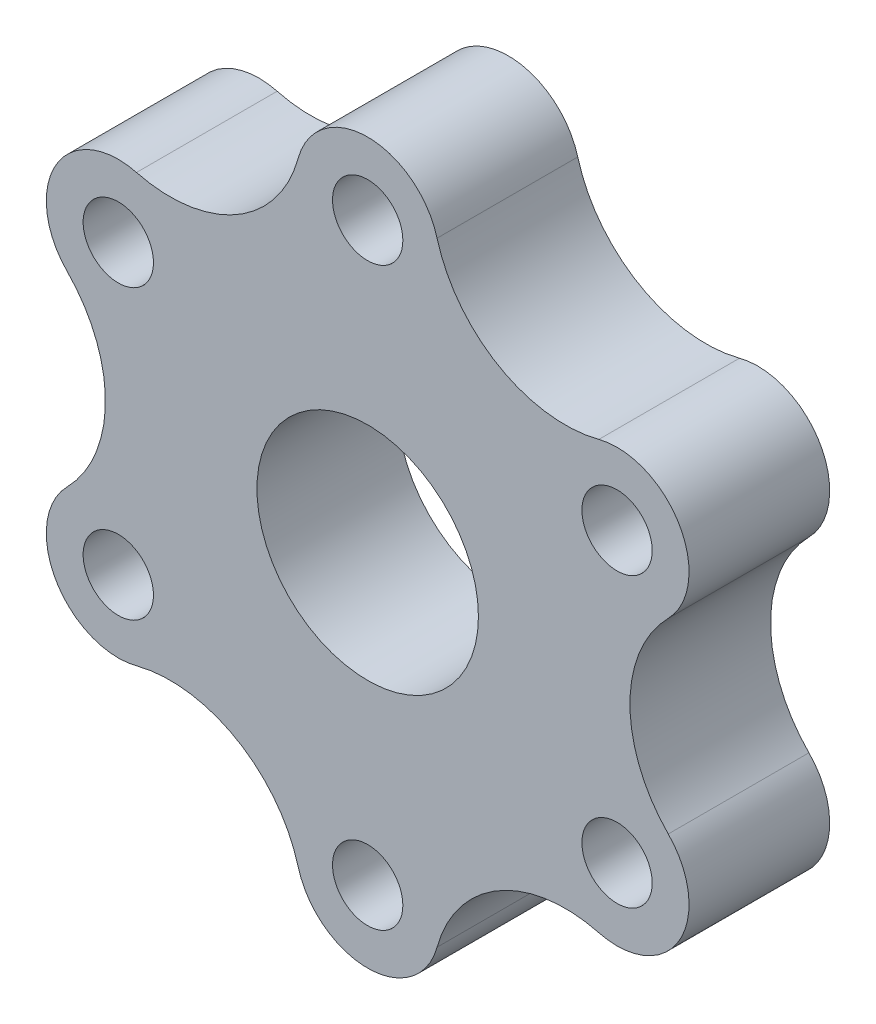
SolidWorks part; units mm, degrees
material "6061-T6 (SS)"
ref_plane "Front Plane" through (0, 0, 0) normal (0, 0, 1) x (1, 0, 0)
ref_plane "Top Plane" through (0, 0, 0) normal (0, 1, 0) x (1, 0, 0)
ref_plane "Right Plane" through (0, 0, 0) normal (1, 0, 0) x (0, 0, -1)
sketch "Sketch1" plane through (0, 0, 0) normal (0, 0, 1) x (1, 0, 0)
  circle A0 centre (0, 0) radius 45 construction
  circle A1 centre (0, 0) radius 37.5 construction
  circle A2 centre (0, 0) radius 10
  arc A3 (6.268, 27.7213) -> (-6.268, 27.7213) centre (0, 26) ccw
  arc A4 (27.1413, 8.4324) -> (20.8734, 19.2888) centre (22.5167, 13) ccw
  arc A5 (20.8734, -19.2888) -> (27.1413, -8.4324) centre (22.5167, -13) ccw
  arc A6 (-6.268, -27.7213) -> (6.268, -27.7213) centre (0, -26) ccw
  arc A7 (-27.1413, -8.4324) -> (-20.8734, -19.2888) centre (-22.5167, -13) ccw
  arc A8 (-20.8734, 19.2888) -> (-27.1413, 8.4324) centre (-22.5167, 13) ccw
  arc A9 (-20.8734, 19.2888) -> (-6.268, 27.7213) centre (-17.8396, 30.899) ccw
  arc A10 (6.268, 27.7213) -> (20.8734, 19.2888) centre (17.8396, 30.899) ccw
  arc A11 (27.1413, 8.4324) -> (27.1413, -8.4324) centre (35.6791, 0) ccw
  arc A12 (20.8734, -19.2888) -> (6.268, -27.7213) centre (17.8396, -30.899) ccw
  arc A13 (-6.268, -27.7213) -> (-20.8734, -19.2888) centre (-17.8396, -30.899) ccw
  arc A14 (-27.1413, -8.4324) -> (-27.1413, 8.4324) centre (-35.6791, 0) ccw
  arc A15 (-27.1413, 8.4324) -> (-20.8734, 19.2888) centre (-22.5167, 13) ccw construction
  arc A16 (-6.268, 27.7213) -> (6.268, 27.7213) centre (0, 26) ccw construction
  arc A17 (20.8734, 19.2888) -> (27.1413, 8.4324) centre (22.5167, 13) ccw construction
  arc A18 (27.1413, -8.4324) -> (20.8734, -19.2888) centre (22.5167, -13) ccw construction
  arc A19 (6.268, -27.7213) -> (-6.268, -27.7213) centre (0, -26) ccw construction
  arc A20 (-20.8734, -19.2888) -> (-27.1413, -8.4324) centre (-22.5167, -13) ccw construction
  circle A21 centre (0, 26) radius 3.175
  circle A22 centre (22.5167, 13) radius 3.175
  circle A23 centre (22.5167, -13) radius 3.175
  circle A24 centre (0, -26) radius 3.175
  circle A25 centre (-22.5167, -13) radius 3.175
  circle A26 centre (-22.5167, 13) radius 3.175
  point P19 (0, 0)
  point P38 (0, 0)
  point P44 (0, 0)
  dimension "D1" = 90
  dimension "D2" = 75
  dimension "D3" = 20
  dimension "D4" = 13
  dimension "D7" = 12
  dimension "D9" = 6.35
  dimension "D5" = 26
  dimension "D6" = 6
  dimension "D8" = 6
  dimension "D10" = 6
extrude "Boss-Extrude1" add sketch "Sketch1" along normal mid plane 12.7
equation "\"D9@Sketch1\"=0.25in"
equation "\"D1@Boss-Extrude1\"=0.5in"
